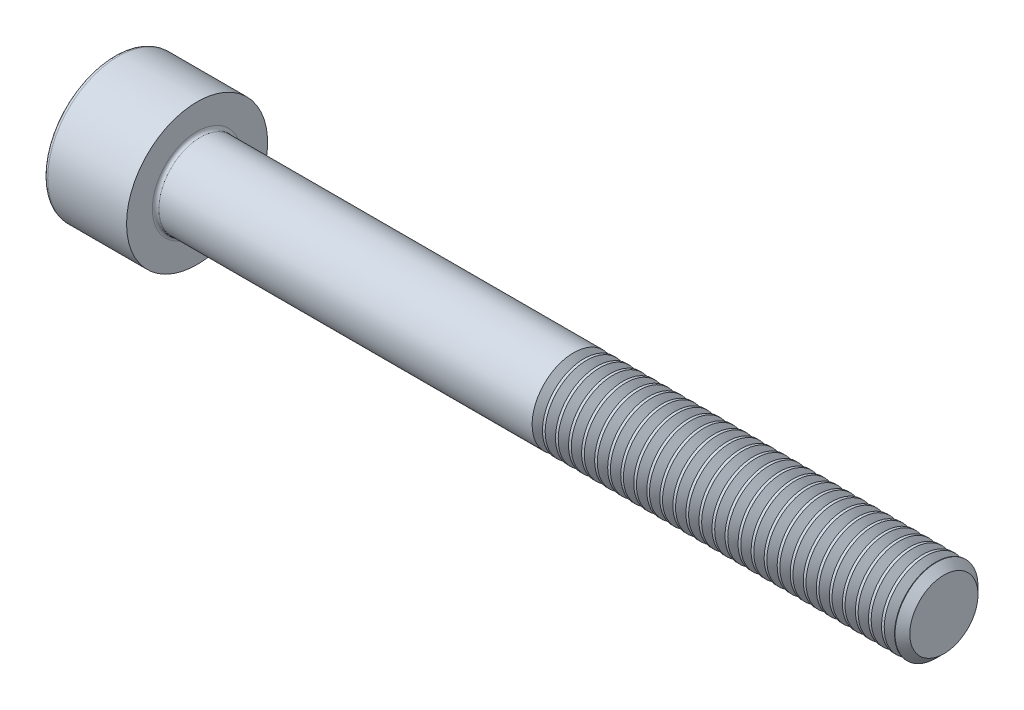
SolidWorks part; units mm, degrees
revolve "Base-Revolve" add sketch "BodySke"
sketch "BodySke" plane through (0, 0, 0) normal (0, 0, 1) x (1, 0, 0)
  line L0 (0, 0) -> (0, 4.25)
  line L1 (0, 4.25) -> (5, 4.25)
  line L2 (5, 4.25) -> (5, 2.5)
  line L3 (5, 2.5) -> (49.555, 2.5)
  line L4 (50, 2.055) -> (50, 0)
  line L5 (50, 0) -> (0, 0)
  line L6 (-31.75, 0) -> (127, 0) construction
  line L8 (50, 2.055) -> (49.555, 2.5)
  line L10 (50, -2.055) -> (49.555, -2.5) construction
  line L11 (5.8, 9.525) -> (5.8, 3.175) construction
  line L12 (28, 9.525) -> (28, 3.175) construction
  line L13 (-10, 9.525) -> (-10, 3.175) construction
  dimension "Diameter" = 5
  dimension "Head_dia" = 8.5
cosmetic thread "ThreadCosmetic" [suppressed]
fillet "Fillet1" radius 0.2 1 edges at (5, 0, 2.5)
fillet "Fillet2" radius 0.25 1 edges at (0, 0, 4.25)
ref_plane "Plane1" through (0, 0, 0) normal (0, 0, 1) x (1, 0, 0)
ref_plane "Plane2" through (0, 0, 0) normal (0, 1, 0) x (1, 0, 0)
ref_plane "Plane3" through (0, 0, 0) normal (1, 0, 0) x (0, 0, -1)
sketch "Sketch2" plane through (0, 0, 0) normal (0, 0, 1) x (1, 0, 0)
  line L0 (0, 2.042) -> (2.5, 2.042)
  line L1 (2.5, 2.042) -> (3.6789, 0)
  line L2 (-31.75, 0) -> (127, 0) construction
  line L3 (3.6789, 0) -> (0, 0)
  line L4 (0, 0) -> (0, 2.042)
  line L6 (0, 0) -> (47.625, 0) construction
  dimension "D1" = 2.042
  dimension "D2" = 60
revolve "Hex-PreBroach" cut sketch "Sketch2" angle 360 about L6
sketch "Sketch3" plane through (0, 0, 0) normal (-1, 0, 0) x (0, 0.5, 0.866)
  line L0 (1.1789, 2.042) -> (-1.1789, 2.042)
  line L1 (-1.1789, 2.042) -> (-2.3579, 0)
  line L2 (1.1789, 2.042) -> (2.3579, 0)
  line L3 (1.1789, -2.042) -> (2.3579, 0)
  line L4 (1.1789, -2.042) -> (-1.1789, -2.042)
  line L5 (-1.1789, -2.042) -> (-2.3579, 0)
  dimension "D1" = 2.042
  dimension "D2" = 2.042
extrude "Hex" cut sketch "Sketch3" against normal blind 2.5
sketch "ThdSchSke" plane through (0, 0, 0) normal (0, 0, 1) x (1, 0, 0)
  line L0 (28, -2.055) -> (27.6884, -2.5)
  line L1 (28, -2.055) -> (28.3116, -2.5)
  line L2 (28.3116, -2.5) -> (28.3116, -3.125)
  line L3 (-3.175, 0) -> (5.1513, 0) construction
  line L4 (0, 4) -> (0, -4) construction
  line L5 (28.3116, -3.125) -> (27.6884, -3.125)
  line L6 (27.6884, -3.125) -> (27.6884, -2.5)
  dimension "Diameter" = 5
  dimension "Thread_minor" = 4.11
  dimension "Start" = 28
revolve "ThreadSchematic" cut sketch "ThdSchSke" angle 360 about L3
pattern_linear "ThdSchPat" count 29 spacing 0.7857 along (1, 0, 0) of "ThreadSchematic"
equation "\"D2@Sketch3\" = \"Hex_size@Sketch3\" / 2"
equation "\"D1@Sketch3\" = \"Hex_size@Sketch3\" / 2"
equation "\"D1@Sketch2\" = \"Hex_size@Sketch3\" / 2"
equation "\"Thread_minor@ThreadCosmetic\"  =  \"Minor_dia@BodySke\""
equation "\"Depth@Sketch2\" =  \"Key_eng@Hex\""
equation "\"Thread_length@ThreadCosmetic\" = ((sgn( (\"Length@BodySke\" - \"Advance@BodySke\" * 3.0) - \"Thread_nom@BodySke\" )-1)*( (\"Length@BodySke\" - \"Advance@BodySke\" * 3.0) - \"Thread_nom@BodySke\" ))/-2+ \"Thread_nom@BodySke\""
equation "\"Thread_minor@ThdSchSke\" = \"Minor_dia@BodySke\""
equation "\"Diameter@ThdSchSke\" = \"Diameter@BodySke\""
equation "\"Overcut@ThdSchSke\" = \"Diameter@BodySke\" * 1.25"
equation "\"Start@ThdSchSke\" = \"Head_ht@BodySke\" + \"Length@BodySke\" - \"Thread_length@ThreadCosmetic\"  '---Non-countersunk---"
equation "\"Num_threads@ThdSchPat\" = int( \"Thread_length@ThreadCosmetic\" / \"Advance@BodySke\" + 0.999 )  + 1"
equation "\"Advance@ThdSchPat\" = \"Thread_length@ThreadCosmetic\" /  (\"Num_threads@ThdSchPat\" - 1) 'relax it"
equation "\"Num_threads@ThdSchPat\" = \"Num_threads@ThdSchPat\" - sgn( \"Num_threads@ThdSchPat\" - 1) '---chamfered tips only---"
